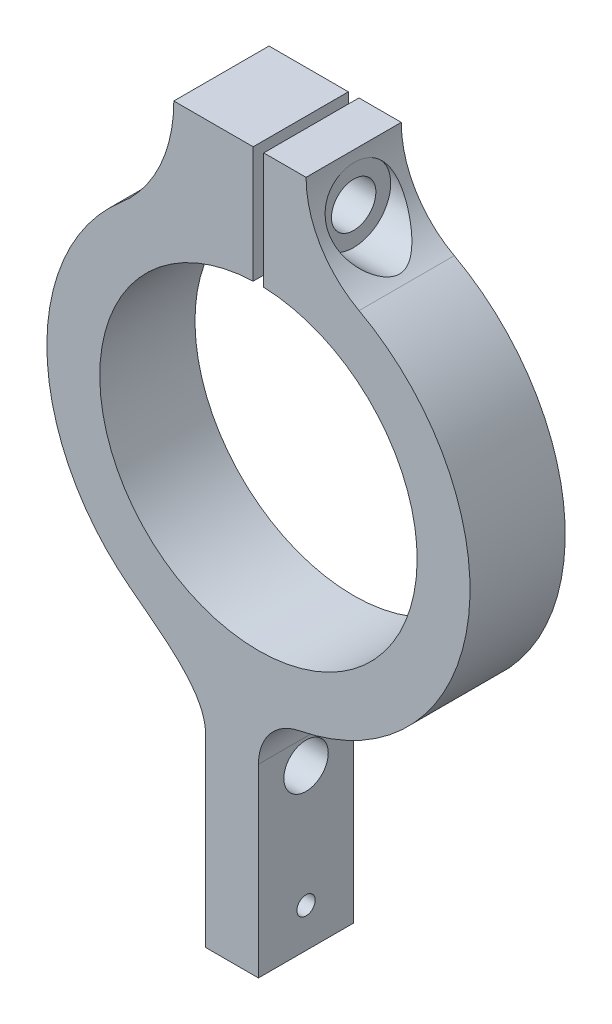
SolidWorks part; units mm, degrees
ref_plane "Front Plane" through (0, 0, 0) normal (0, 0, 1) x (1, 0, 0)
ref_plane "Top Plane" through (0, 0, 0) normal (0, 1, 0) x (1, 0, 0)
ref_plane "Right Plane" through (0, 0, 0) normal (1, 0, 0) x (0, 0, -1)
sketch "Sketch1" plane through (0, 0, 0) normal (0, 0, 1) x (1, 0, 0)
  line L0 (0, 0) -> (0, 40) construction
  line L1 (0, -48.6004) -> (0, -83.6004)
  line L2 (0, -83.6004) -> (-10, -83.6004)
  line L3 (-10, -83.6004) -> (-10, -48.6004)
  line L4 (30, 0) -> (40, 0) construction
  line L6 (0, 40) -> (0, 52) construction
  line L7 (0, 52) -> (1, 52) construction
  line L8 (1, 52) -> (1, 29.9833)
  line L9 (1, 52) -> (9, 52)
  line L11 (0, 52) -> (-1, 52) construction
  line L12 (-1, 52) -> (-1, 29.9833)
  line L13 (-1, 52) -> (-16, 52)
  arc A0 (-1, 29.9833) -> (1, 29.9833) centre (0, 0) ccw
  arc A1 (0, -48.6004) -> (7.6931, -39.2532) centre (9.525, -48.6004) cw
  arc A2 (0, 40) -> (-1, 39.9875) centre (0, 0) ccw construction
  arc A3 (9, 52) -> (19.0232, 35.1869) centre (28.1129, 52) ccw
  arc A4 (-25.9512, 30.439) -> (-26.5352, -29.9313) centre (0, 0) ccw
  circle A5 centre (0, 0) radius 40 construction
  arc A6 (-25.9512, 30.439) -> (-16, 52) centre (-44.3333, 52) ccw
  arc A8 (7.6931, -39.2532) -> (19.0232, 35.1869) centre (0, 0) ccw
  spline S0 degree 3 poles (-26.5352, -29.9313) (-20.9482, -34.8844) (-10, -40.904) (-10, -48.6004) knots 0 0 0 0 1 1 1 1
  point P27 (0, -40)
  dimension "D1" = 60
  dimension "D3" = 35
  dimension "D4" = 10
  dimension "D2" = 10
  dimension "D11" = 9.525
  dimension "D6" = 12
  dimension "D7" = 1
  dimension "D8" = 8
  dimension "D9" = 1
  dimension "D10" = 15
extrude "main body" add sketch "Sketch1" along normal blind 18
sketch "Sketch7" plane through (1, 0, 0) normal (-1, 0, 0) x (0, 0, 1)
  line L3 (9, 43) -> (9, 52) construction
  line L4 (18, 52) -> (0, 52) construction
  line L5 (9, 43) -> (0, 43) construction
  line L6 (0, 52) -> (0, 35.1869) construction
  circle A0 centre (9, 43) radius 4
  dimension "D1" = 8
sketch "Sketch12" plane through (0, 0, 0) normal (1, 0, 0) x (0, 0, -1)
  circle A0 centre (-9, -53.34) radius 4
  circle A1 centre (-9, -53.34) radius 7 construction
  circle A2 centre (-9, -76.2) radius 4
  circle A3 centre (-9, -76.2) radius 7 construction
  point P1 (0, 0)
  point P2 (0, 0)
  dimension "D1" = 8
  dimension "D2" = 14
  dimension "D3" = 14
  dimension "D4" = 8
  dimension "D6" = 22.86
  dimension "D5" = 76.2
hole_wizard "M8 Clearance Hole1" positions "Sketch13" profile "Sketch14" hole size "M8" standard "ANSI Metric" end condition through all
sketch "Sketch13" plane through (1, 0, 0) normal (-1, 0, 0) x (0, 0, 1)
  point P0 (9, 43)
sketch "Sketch14" plane through (1, 43, 9) normal (0, 1, 0) x (0, 0, 1)
  line L0 (0, 0) -> (0, 39)
  line L1 (0, 39) -> (4.2, 39)
  line L2 (4.2, 39) -> (4.2, 0)
  line L5 (4.2, 0) -> (0, 0)
  line L11 (0, -6.35) -> (0, 107.95) construction
  dimension "Thru Hole Dia." = 8.4
  dimension "Thru Hole Depth" = 39
hole_wizard "M8 Clearance Hole2" positions "Sketch15" profile "Sketch16" hole size "M8" standard "ANSI Metric" end condition through all
sketch "Sketch15" plane through (1, 0, 0) normal (-1, 0, 0) x (0, 0, 1)
  point P0 (9, 43)
sketch "Sketch16" plane through (1, 43, 9) normal (0, 1, 0) x (0, 0, -1)
  line L0 (0, 0) -> (0, 41)
  line L1 (0, 41) -> (4.2, 41)
  line L2 (4.2, 41) -> (4.2, 0)
  line L5 (4.2, 0) -> (0, 0)
  line L11 (0, -6.35) -> (0, 107.95) construction
  dimension "Thru Hole Dia." = 8.4
  dimension "Thru Hole Depth" = 41
sketch "Sketch17" plane through (0, 0, 18) normal (0, 0, 1) x (1, 0, 0)
  line L0 (-16, 52) -> (-16, 25.3772)
  line L1 (9, 52) -> (9, 28.6182)
  arc A0 (-1, 29.9833) -> (1, 29.9833) centre (0, 0) ccw construction
hole_wizard "M8 Clearance Hole3" positions "Sketch18" profile "Sketch19" hole size "M8" standard "ANSI Metric" end condition through all
sketch "Sketch18" plane through (0, 0, 0) normal (1, 0, 0) x (0, 0, -1)
  point P0 (-9, -53.34)
  point P6 (0, 0)
sketch "Sketch19" plane through (0, -53.34, 9) normal (0, 1, 0) x (0, 0, -1)
  line L0 (0, 0) -> (0, 40)
  line L1 (0, 40) -> (4.2, 40)
  line L2 (4.2, 40) -> (4.2, 0)
  line L5 (4.2, 0) -> (0, 0)
  line L11 (0, -6.35) -> (0, 107.95) construction
  dimension "Thru Hole Dia." = 8.4
  dimension "Thru Hole Depth" = 40
ref_plane "Plane1" through (-16, 0, 0) normal (-1, 0, 0) x (0, 0, 1)
sketch "Sketch26" plane through (-16, 0, 0) normal (-1, 0, 0) x (0, 0, 1)
  circle A0 centre (9, 43) radius 7
  dimension "D1" = 14
ref_plane "Plane2" through (9, 0, 0) normal (1, 0, 0) x (0, 0, -1)
sketch "Sketch27" plane through (9, 0, 0) normal (1, 0, 0) x (0, 0, -1)
  circle A0 centre (-9, 43) radius 7
  circle A1 centre (-9, 43) radius 7 construction
extrude "Cut-Extrude2" cut sketch "Sketch27" along normal through all
sketch "Sketch29" plane through (0, 0, 18) normal (0, 0, 1) x (1, 0, 0)
  line L0 (-16, 52) -> (-42.54, 52) construction
  line L1 (-42.54, 52) -> (-42.54, 0) construction
  line L2 (-42.54, 0) -> (-40, 0) construction
  arc A0 (-25.9512, 30.439) -> (-26.5352, -29.9313) centre (0, 0) ccw construction
  dimension "D1" = 2.54
hole_wizard "#8-32 Tapped Hole1" positions "Sketch30" profile "Sketch32" tap size "#8-32" standard "ANSI Inch" end condition through all
sketch "Sketch30" plane through (0, 0, 0) normal (1, 0, 0) x (0, 0, -1)
  point P0 (-9, -76.2)
sketch "Sketch32" plane through (0, -76.2, 9) normal (0, 1, 0) x (0, 0, -1)
  line L0 (0, 0) -> (0, 40)
  line L1 (0, 40) -> (1.7272, 40)
  line L2 (1.7272, 40) -> (1.7272, 0)
  line L5 (1.7272, 0) -> (0, 0)
  line L11 (0, -6.35) -> (0, 107.95) construction
  dimension "Thru Tap Drill Dia." = 3.4544
  dimension "Thru Tap Drill Depth" = 40
cosmetic thread "Hole Thread1" parameters "D2"=4.1656
